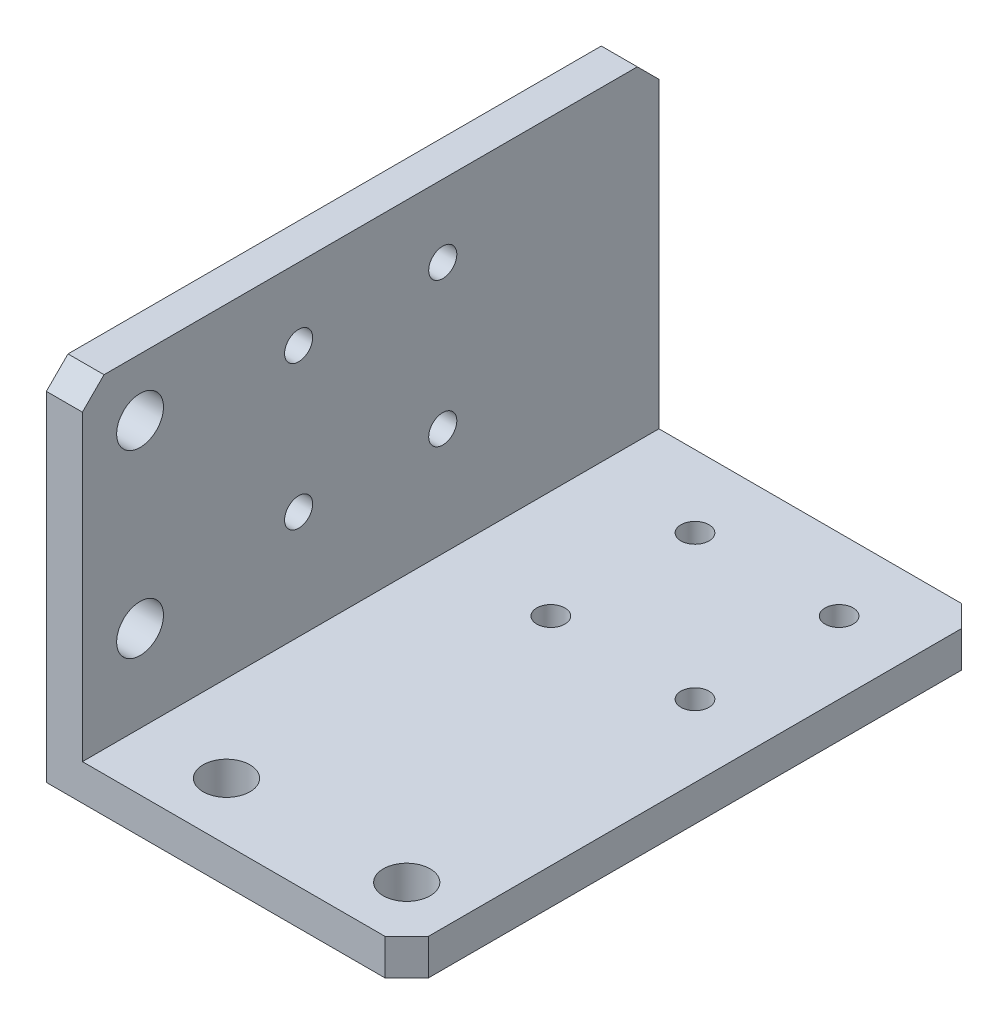
SolidWorks part; units mm, degrees
material "Lega 1060"
ref_plane "Piano frontale" through (0, 0, 0) normal (0, 0, 1) x (1, 0, 0)
ref_plane "Piano superiore" through (0, 0, 0) normal (0, 1, 0) x (1, 0, 0)
ref_plane "Piano destro" through (0, 0, 0) normal (1, 0, 0) x (0, 0, -1)
sketch "Schizzo1" plane through (0, 0, 0) normal (0, 0, 1) x (1, 0, 0)
  line L0 (0, 0) -> (0, 50)
  line L1 (0, 50) -> (5, 50)
  line L2 (5, 50) -> (5, 5)
  line L3 (5, 5) -> (50, 5)
  line L4 (50, 5) -> (50, 0)
  line L5 (50, 0) -> (0, 0)
  dimension "D1" = 5
  dimension "D2" = 5
  dimension "D3" = 50
  dimension "D4" = 50
extrude "Estrusione-Estrusione1" add sketch "Schizzo1" along normal blind 80
sketch "Schizzo2" plane through (0, 0, 0) normal (0, -1, 0) x (1, 0, 0)
  line L0 (5.4524, 72) -> (42.7933, 72) construction
  line L1 (0, 80) -> (50, 80) construction
  line L5 (50, 80) -> (50, 0) construction
  point P4 (17, 72)
  point P5 (42, 72)
  dimension "D1" = 8
  dimension "D2" = 25
  dimension "D3" = 8
sketch "Schizzo3" plane through (0, 0, 0) normal (-1, 0, 0) x (0, 0, 1)
  line L0 (72, 44.621) -> (72, 5.772) construction
  line L1 (80, 50) -> (80, 0) construction
  line L2 (80, 50) -> (0, 50) construction
  point P4 (72, 42)
  point P5 (72, 17)
  dimension "D1" = 8
  dimension "D2" = 8
  dimension "D3" = 25
hole_wizard "Foro Ø6.5 (6.5)-1" positions "Schizzo5" profile "Schizzo4" hole size "Ø6.5" standard "ISO" end condition through all
sketch "Schizzo5" plane through (0, 0, 0) normal (0, -1, 0) x (-1, 0, 0)
  point P0 (-17, -72)
  point P3 (-42, -72)
sketch "Schizzo4" plane through (17, 0, 72) normal (1, 0, 0) x (0, 0, -1)
  line L0 (0, 0) -> (0, 50)
  line L1 (0, 50) -> (3.25, 50)
  line L2 (3.25, 50) -> (3.25, 0)
  line L5 (3.25, 0) -> (0, 0)
  line L11 (0, -6.35) -> (0, 107.95) construction
  dimension "Thru Hole Dia." = 6.5
  dimension "Thru Hole Depth" = 50
hole_wizard "Foro Ø6.5 (6.5)-2" positions "Schizzo7" profile "Schizzo6" hole size "Ø6.5" standard "ISO"
sketch "Schizzo7" plane through (0, 0, 0) normal (-1, 0, 0) x (0, 0, 1)
  point P1 (72, 42)
  point P4 (72, 17)
sketch "Schizzo6" plane through (0, 42, 72) normal (0, 1, 0) x (0, 0, 1)
  line L0 (0, 0) -> (0, 6.9528)
  line L1 (0, 6.9528) -> (3.25, 5)
  line L2 (3.25, 5) -> (3.25, 0)
  line L5 (3.25, 0) -> (0, 0)
  line L10 (0, 6.9528) -> (-3.25, 5) construction
  line L11 (0, -6.35) -> (0, 107.95) construction
  dimension "Hole Dia." = 6.5
  dimension "Hole Depth" = 5
  dimension "Drill Angle" = 118
ref_plane "Piano1" through (0, 0, 40) normal (0, 0, 1) x (1, 0, 0)
sketch "Schizzo8" plane through (0, 0, 0) normal (0, -1, 0) x (1, 0, 0)
  line L0 (30, 20) -> (7.0316, 20) construction
  line L1 (30, 20) -> (22.8949, 12.8949) construction
  line L2 (0, 80) -> (50, 80) construction
  line L3 (50, 80) -> (50, 0) construction
  circle A0 centre (20, 10) radius 1.75
  circle A1 centre (20, 30) radius 1.75
  circle A2 centre (40, 30) radius 1.75
  circle A3 centre (40, 10) radius 1.75
  point P18 (30, 20)
  dimension "D3" = 3.5
  dimension "D1" = 60
  dimension "D2" = 20
  dimension "D4" = 45
  dimension "D5" = 20
  dimension "D6" = 4
sketch "Schizzo9" plane through (0, 0, 0) normal (-1, 0, 0) x (0, 0, 1)
  line L0 (40, 44.574) -> (40, 30) construction
  line L1 (40, 30) -> (33.014, 36.986) construction
  line L2 (80, 50) -> (0, 50) construction
  line L3 (80, 50) -> (80, 0) construction
  circle A0 centre (30, 40) radius 1.75
  circle A1 centre (50, 40) radius 1.75
  circle A2 centre (50, 20) radius 1.75
  circle A3 centre (30, 20) radius 1.75
  point P18 (40, 30)
  dimension "D4" = 3.5
  dimension "D1" = 20
  dimension "D2" = 40
  dimension "D3" = 45
  dimension "D5" = 20
  dimension "D6" = 4
chamfer "Smusso1" distance 3 angle 45 4 edges at (2.5, 50, 0) (50, 2.5, 0) (50, 2.5, 80) (2.5, 50, 80)
hole_wizard "M3.5 Clearance Hole1" positions "3DSketch1" profile "Sketch1" hole size "M3.5" standard "ISO" end condition through all
sketch3d "3DSketch1"
  point P0 (20, 0, 30)
  point P3 (40, 0, 30)
  point P6 (40, 0, 10)
  point P9 (20, 0, 10)
sketch "Sketch1" plane through (20, 0, 30) normal (1, 0, 0) x (0, 0, -1)
  line L0 (0, 0) -> (0, 50)
  line L1 (0, 50) -> (1.95, 50)
  line L2 (1.95, 50) -> (1.95, 0)
  line L5 (1.95, 0) -> (0, 0)
  line L11 (0, -6.35) -> (0, 107.95) construction
  dimension "Thru Hole Dia." = 3.9
  dimension "Thru Hole Depth" = 50
hole_wizard "M3.5 Clearance Hole2" positions "3DSketch2" profile "Sketch2" hole size "M3.5" standard "ISO" end condition through all
sketch3d "3DSketch2"
  point P0 (0, 40, 30)
  point P3 (0, 40, 50)
  point P6 (0, 20, 50)
  point P9 (0, 20, 30)
sketch "Sketch2" plane through (0, 40, 30) normal (0, 1, 0) x (0, 0, 1)
  line L0 (0, 0) -> (0, 50)
  line L1 (0, 50) -> (1.95, 50)
  line L2 (1.95, 50) -> (1.95, 0)
  line L5 (1.95, 0) -> (0, 0)
  line L11 (0, -6.35) -> (0, 107.95) construction
  dimension "Thru Hole Dia." = 3.9
  dimension "Thru Hole Depth" = 50
sketch "Sketch3" plane through (0, 0, 0) normal (0, -1, 0) x (1, 0, 0)
  line L0 (0, 80) -> (47, 80) construction
  line L1 (0, 80) -> (0, 0) construction
  point P0 (5, 80)
  dimension "D1" = 5
